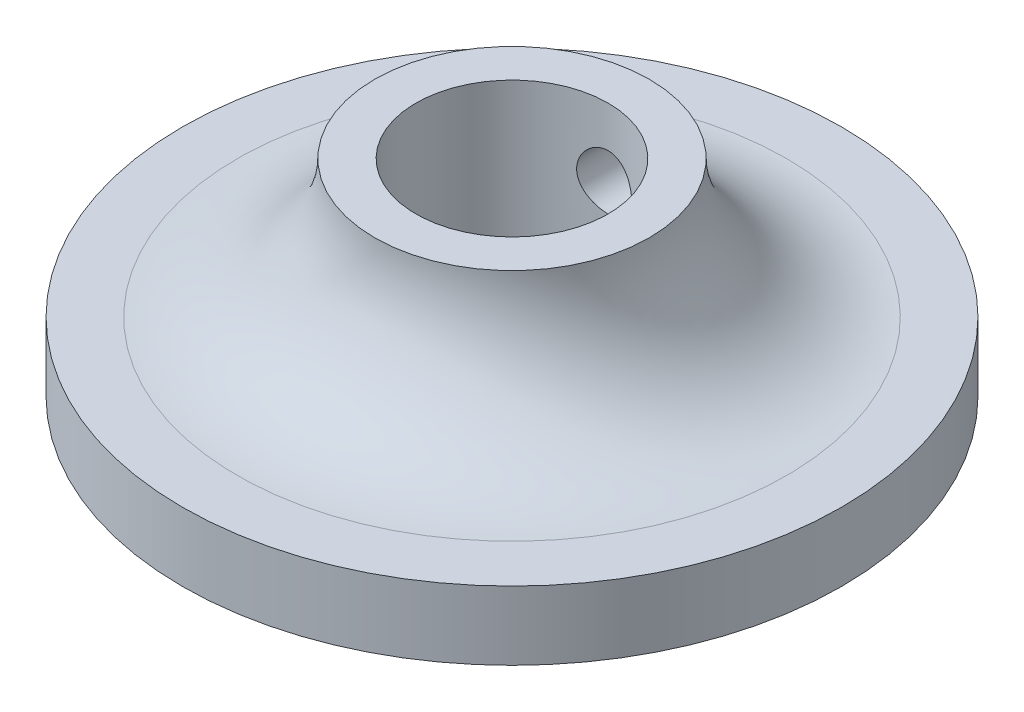
SolidWorks part; units mm, degrees
ref_plane "Спереди" through (0, 0, 0) normal (0, 0, 1) x (1, 0, 0)
ref_plane "Сверху" through (0, 0, 0) normal (0, 1, 0) x (1, 0, 0)
ref_plane "Справа" through (0, 0, 0) normal (1, 0, 0) x (0, 0, -1)
sketch "Эскиз1" plane through (0, 0, 0) normal (0, 0, 1) x (1, 0, 0)
  line L1 (-120, 0) -> (-120, 25)
  line L2 (-120, 25) -> (-100, 25)
  line L3 (-50, 75) -> (-35, 75)
  line L4 (-35, 75) -> (-35, 25)
  line L7 (-120, 0) -> (0, 0)
  line L12 (0, 0) -> (0, 25)
  line L13 (0, 25) -> (-35, 25)
  arc A0 (-100, 25) -> (-50, 75) centre (-100, 75) ccw
  dimension "D1" = 75
  dimension "D2" = 25
  dimension "D3" = 15
  dimension "D4" = 20
  dimension "D5" = 35
revolve "Повернуть3" add sketch "Эскиз1" angle 360 about L12
ref_plane "Плоскость5" through (0, 0, -40) normal (0, 0, 1) x (1, 0, 0)
sketch "Эскиз3" plane through (0, 0, -40) normal (0, 0, 1) x (1, 0, 0)
  line L0 (50, 75) -> (-50, 75) construction
  line L1 (0, 0) -> (0, 75) construction
  circle A0 centre (0, 50) radius 10
  point P4 (0, 0)
  dimension "D1" = 20
  dimension "D2" = 25
extrude "Вырез-Вытянуть2" cut sketch "Эскиз3" against normal through all and the other way blind 30
